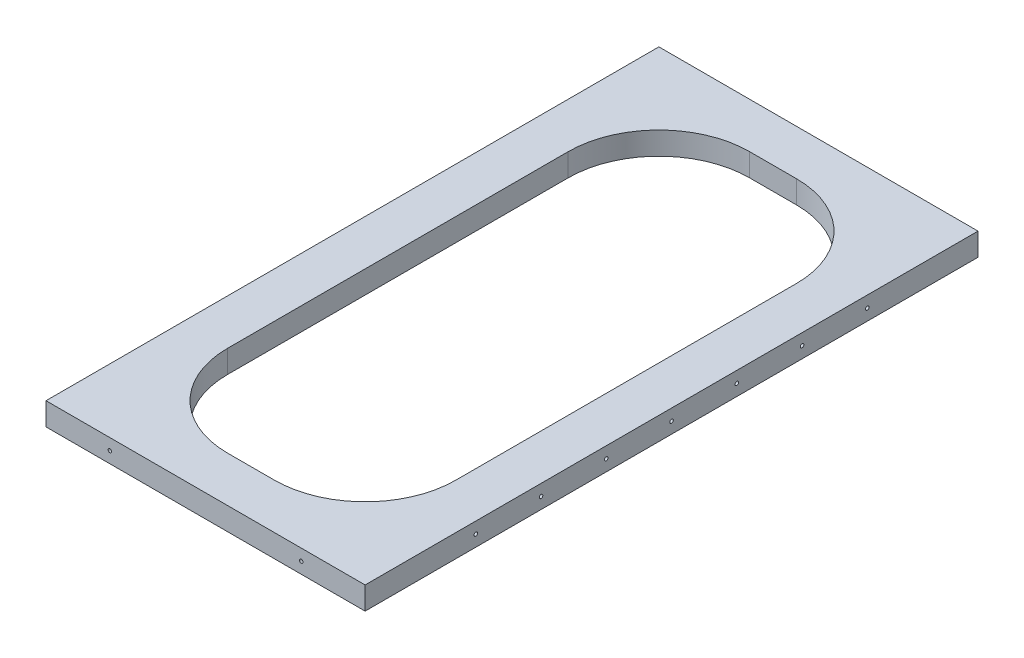
SolidWorks part; units mm, degrees
material "MDF"
ref_plane "Front" through (0, 0, 0) normal (0, 0, 1) x (1, 0, 0)
ref_plane "Top" through (0, 0, 0) normal (0, 1, 0) x (1, 0, 0)
ref_plane "Right" through (0, 0, 0) normal (1, 0, 0) x (0, 0, -1)
sketch "Sketch1" plane through (0, 0, 0) normal (0, 0, 1) x (1, 0, 0)
  line L0 (-271.672, -233.3625) -> (-271.672, -196.215) construction
  line L1 (-271.672, -193.04) -> (-93.1354, -193.04)
  line L2 (-271.672, -193.04) -> (-271.672, -180.34)
  line L3 (-271.672, -180.34) -> (-93.1354, -180.34)
  line L4 (-93.1354, -193.04) -> (-93.1354, -180.34)
  line L6 (-93.1354, -233.3625) -> (-93.1354, -196.215) construction
  line L7 (-93.1354, -196.215) -> (-271.672, -196.215) construction
  dimension "D1" = 12.7
  dimension "D2" = 3.175
extrude "Boss-Extrude1" add sketch "Sketch1" along normal up to surface (342.9 mm away)
sketch "Sketch2" plane through (0, -193.04, 0) normal (0, -1, 0) x (1, 0, 0)
  line L0 (-118.5354, 317.5) -> (-246.272, 317.5)
  line L1 (-246.272, 317.5) -> (-246.272, 25.4)
  line L2 (-246.272, 25.4) -> (-118.5354, 25.4)
  line L3 (-118.5354, 25.4) -> (-118.5354, 317.5)
  line L4 (-93.1354, 342.9) -> (-271.672, 342.9)
  line L5 (-271.672, 342.9) -> (-271.672, 0)
  line L6 (-271.672, 0) -> (-93.1354, 0)
  line L7 (-93.1354, 0) -> (-93.1354, 342.9)
  line L8 (-93.1354, 342.9) -> (-271.672, 342.9) construction
  line L9 (-271.672, 342.9) -> (-271.672, 0) construction
  line L10 (-271.672, 0) -> (-93.1354, 0) construction
  line L11 (-93.1354, 0) -> (-93.1354, 342.9) construction
  dimension "D1" = 0
  dimension "D2" = 25.4
extrude "Cut-Extrude1" cut sketch "Sketch2" against normal up to next
fillet "Fillet1" radius 50.8 4 edges at (-246.272, -186.69, 317.5) (-118.5354, -186.69, 317.5) (-118.5354, -186.69, 25.4) (-246.272, -186.69, 25.4)
hole_wizard "15/64 (0.23438) Diameter Hole2" positions "Sketch5" profile "Sketch6" hole size "15/64" standard "ANSI Inch"
sketch "Sketch5" plane through (-182.4037, 1936.854, -6.35) normal (0, 0, -1) x (1, 0, 0)
  point P0 (-262.8265, 2051.0885)
  point P3 (-262.8265, 2014.0687)
  point P6 (-262.8265, 1977.0488)
  point P9 (-98.7933, 2115.9598)
  point P12 (-98.7933, 2151.1665)
  point P15 (-44.6341, 2123.544)
  point P18 (0, 2123.544)
  point P21 (44.6341, 2123.544)
sketch "Sketch6" plane through (-445.2302, -114.2346, -6.35) normal (1, 0, 0) x (0, 1, 0)
  line L0 (0, 0) -> (0, 14.4885)
  line L1 (0, 14.4885) -> (2.9766, 12.7)
  line L2 (2.9766, 12.7) -> (2.9766, 0)
  line L3 (2.9766, 0) -> (0, 0)
  line L4 (0, 14.4885) -> (-2.9766, 12.7) construction
  line L5 (0, -6.35) -> (0, 107.95) construction
  dimension "Hole Dia." = 5.9533
  dimension "Hole Depth" = 12.7
  dimension "Drill Angle" = 118
hole_wizard "5/64 (0.07813) Diameter Hole1" positions "Sketch7" profile "Sketch8" hole size "5/64" standard "ANSI Inch"
sketch "Sketch7" plane through (-182.4037, 1936.854, 361.95) normal (0, 0, 1) x (-1, 0, 0)
  line L23 (262.8265, 2088.1084) -> (262.8265, 2038.7486)
  line L24 (262.8265, 2038.7486) -> (262.8265, 1989.3888)
  line L25 (262.8265, 1989.3888) -> (262.8265, 2038.7486)
  line L26 (262.8265, 2038.7486) -> (262.8265, 1989.3888)
  line L27 (262.8265, 1989.3888) -> (262.8265, 1940.029)
  line L33 (98.7933, 2170.2165) -> (98.7933, 2131.8519)
  line L35 (98.7933, 2131.8519) -> (98.7933, 2093.4873)
  line L36 (98.7933, 2093.4873) -> (98.7933, 2055.1227)
  line L37 (98.7933, 2055.1227) -> (98.7933, 2016.7581)
  line L38 (98.7933, 2016.7581) -> (98.7933, 1978.3935)
  line L39 (98.7933, 1978.3935) -> (98.7933, 1940.029)
  line L44 (89.2683, 2123.544) -> (53.561, 2123.544)
  line L46 (53.561, 2123.544) -> (17.8537, 2123.544)
  line L48 (-17.8537, 2123.544) -> (-53.561, 2123.544)
  line L49 (-53.561, 2123.544) -> (-89.2683, 2123.544)
  line L53 (0, 2170.2165) -> (0.2777, 1940.029) construction
  line L55 (-98.3301, 1978.1557) -> (-98.2375, 1939.7912)
  line L56 (-98.4227, 2016.5202) -> (-98.3301, 1978.1557)
  line L57 (-98.5153, 2054.8846) -> (-98.4227, 2016.5202)
  line L58 (-98.6078, 2093.2491) -> (-98.5153, 2054.8846)
  line L59 (-98.7004, 2131.6136) -> (-98.6078, 2093.2491)
  line L60 (-98.793, 2169.978) -> (-98.7004, 2131.6136)
  line L61 (-262.3894, 1988.755) -> (-262.2702, 1939.3954)
  line L62 (-262.5085, 2038.1147) -> (-262.3894, 1988.755)
  line L63 (-262.3894, 1988.755) -> (-262.5085, 2038.1147)
  line L64 (-262.5085, 2038.1147) -> (-262.3894, 1988.755)
  line L65 (-262.6276, 2087.4744) -> (-262.5085, 2038.1147)
  point P61 (262.8265, 2038.7486)
  point P63 (262.8265, 1989.3888)
  point P71 (262.8265, 1964.7089)
  point P75 (262.8265, 2014.0687)
  point P79 (262.8265, 2063.4285)
  point P95 (98.7933, 2131.8519)
  point P99 (98.7933, 2093.4873)
  point P100 (98.7933, 2055.1227)
  point P102 (98.7933, 2016.7581)
  point P103 (98.7933, 1978.3935)
  point P126 (53.561, 2123.544)
  point P134 (-53.561, 2123.544)
  point P162 (-98.3301, 1978.1557)
  point P163 (-98.4227, 2016.5202)
  point P164 (-98.5153, 2054.8846)
  point P165 (-98.6078, 2093.2491)
  point P166 (-98.7004, 2131.6136)
  point P167 (-262.568, 2062.7945)
  point P168 (-262.4489, 2013.4349)
  point P169 (-262.3298, 1964.0752)
  point P170 (-262.3894, 1988.755)
  point P171 (-262.5085, 2038.1147)
sketch "Sketch8" plane through (80.1047, -101.2608, 361.95) normal (1, 0, 0) x (0, -1, 0)
  line L0 (0, 0) -> (0, 38.6962)
  line L1 (0, 38.6962) -> (0.9923, 38.1)
  line L2 (0.9923, 38.1) -> (0.9923, 4.7024)
  line L3 (0.9923, 4.7024) -> (5.08, 0)
  line L4 (5.08, 0) -> (0, 0)
  line L5 (-0.9923, 4.7024) -> (-5.08, 0) construction
  line L6 (0, 38.6962) -> (-0.9923, 38.1) construction
  line L7 (0, -6.35) -> (0, 107.95) construction
  dimension "Hole Dia." = 1.9845
  dimension "Hole Depth" = 38.1
  dimension "Near C'Sink Dia." = 10.16
  dimension "Near C'Sink Angle" = 82
  dimension "Drill Angle" = 118
hole_wizard "5/64 (0.07813) Diameter Hole2" positions "Sketch9" profile "Sketch10" hole size "5/64" standard "ANSI Inch"
sketch "Sketch9" plane through (-271.672, 0, 0) normal (-1, 0, 0) x (0, 0, 1)
  point P0 (280.9875, -186.69)
  point P3 (244.475, -186.69)
  point P6 (207.9625, -186.69)
  point P9 (171.45, -186.69)
  point P12 (134.9375, -186.69)
  point P15 (98.425, -186.69)
  point P18 (61.9125, -186.69)
sketch "Sketch10" plane through (-271.672, -186.69, 280.9875) normal (0, 1, 0) x (0, 0, 1)
  line L0 (0, 0) -> (0, 19.6462)
  line L1 (0, 19.6462) -> (0.9923, 19.05)
  line L2 (0.9923, 19.05) -> (0.9923, 0)
  line L5 (0.9923, 0) -> (0, 0)
  line L10 (0, 19.6462) -> (-0.9923, 19.05) construction
  line L11 (0, -6.35) -> (0, 107.95) construction
  dimension "Hole Dia." = 1.9845
  dimension "Hole Depth" = 19.05
  dimension "Drill Angle" = 118
ref_plane "Plane1" through (-182.4037, 0, 0) normal (-1, 0, 0) x (0, 0, 1)
mirror "Mirror1" about plane through (-182.4037, 0, 0) normal (-1, 0, 0) of "5/64 (0.07813) Diameter Hole2"
